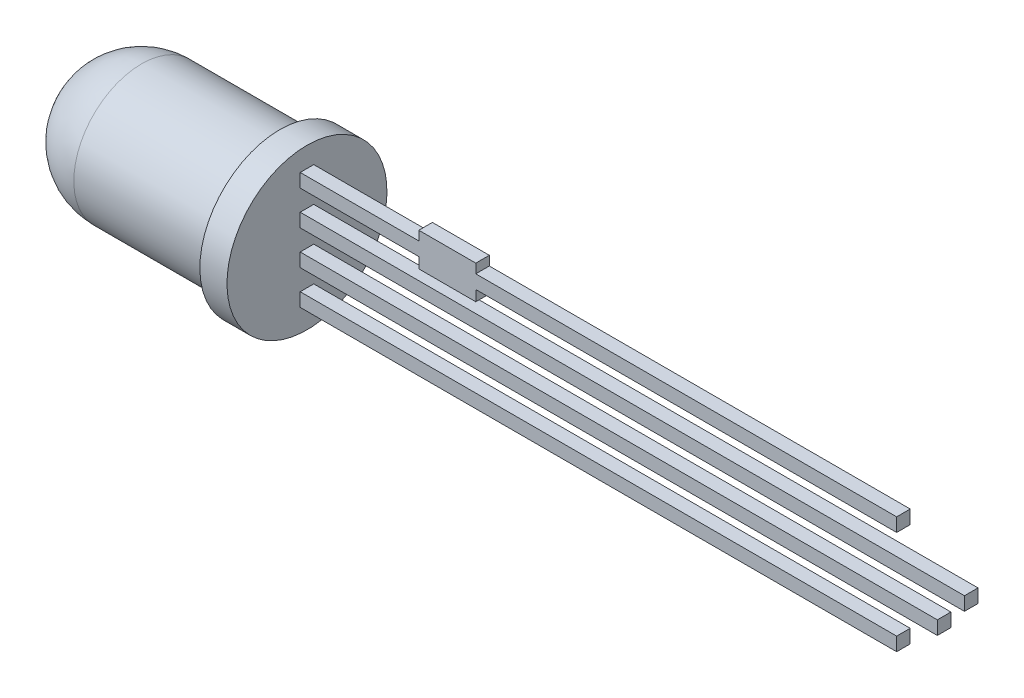
SolidWorks part; units mm, degrees
ref_plane "Front Plane" through (0, 0, 0) normal (0, 0, 1) x (1, 0, 0)
ref_plane "Top Plane" through (0, 0, 0) normal (0, 1, 0) x (1, 0, 0)
ref_plane "Right Plane" through (0, 0, 0) normal (1, 0, 0) x (0, 0, -1)
sketch "Sketch1" plane through (0, 0, 0) normal (0, 0, 1) x (1, 0, 0)
  line L0 (-6, 0) -> (-6, -2.95)
  line L1 (0, 0) -> (-6, 0) construction
  line L2 (-6, -2.95) -> (-7, -2.95)
  line L3 (-7, -2.95) -> (-7, -2.5)
  line L4 (-7, -2.5) -> (-12.1, -2.5)
  line L5 (-6, 0) -> (-14.6, 0) construction
  line L6 (-6, 0) -> (-14.6, 0)
  arc A0 (-14.6, 0) -> (-12.1, -2.5) centre (-12.1, 0) ccw
  point P9 (0, 0)
  point P10 (-14.6143, 0)
  dimension "D1" = 2.95
  dimension "D2" = 1
  dimension "D3" = 5
  dimension "D4" = 8.6
  dimension "D5" = 6
  dimension "D6" = 2.5
revolve "Revolve1" add sketch "Sketch1" angle 360 about L6
sketch "Sketch2" plane through (0, 0, 0) normal (0, 0, 1) x (1, 0, 0)
  line L0 (-6, 2.2047) -> (16, 2.2047)
  line L2 (-6, -2.95) -> (-6, 2.95) construction
  line L3 (16, 2.2047) -> (16, 1.7047)
  line L4 (16, 1.7047) -> (-6, 1.7047)
  line L5 (-6, 1.7047) -> (-6, 0.9347)
  line L6 (-6, 0.9347) -> (18.5, 0.9347)
  line L7 (18.5, 0.9347) -> (18.5, 0.4347)
  line L8 (18.5, 0.4347) -> (-6, 0.4347)
  line L9 (-6, 0.4347) -> (-6, -0.3353)
  line L10 (-6, -0.3353) -> (17.5, -0.3353)
  line L11 (17.5, -0.3353) -> (17.5, -0.8353)
  line L12 (17.5, -0.8353) -> (-6, -0.8353)
  line L13 (-6, -0.8353) -> (-6, -1.6053)
  line L14 (-6, -1.6053) -> (16, -1.6053)
  line L15 (16, -1.6053) -> (16, -2.1053)
  line L16 (16, -2.1053) -> (-6, -2.1053)
  line L17 (-6, -2.1053) -> (-6, 2.2047)
  line L19 (-1.6237, 2.5471) -> (0.4764, 2.5471)
  line L20 (-1.6237, 2.5471) -> (-1.6237, 1.3118)
  line L21 (-1.6237, 1.3118) -> (0.4764, 1.3118)
  line L22 (0.4764, 2.5471) -> (0.4764, 1.3118)
  dimension "D1" = 0.5
  dimension "D2" = 0.5
  dimension "D3" = 0.5
  dimension "D4" = 0.5
  dimension "D5" = 1.27
  dimension "D6" = 1.27
  dimension "D7" = 1.27
  dimension "D8" = 24.5
  dimension "D9" = 2.5
  dimension "D10" = 2.5
  dimension "D11" = 1
extrude "Boss-Extrude1" add sketch "Sketch2" along normal blind 0.25 and the other way blind 0.25 contours L17 L4 L3 L0 | L17 L8 L7 L6 | L17 L12 L11 L10 | L17 L16 L15 L14 | L20 L0 L17 L4 | L19 L22 L21 L20 region at (5, -1.8553, 0) region at (5.75, -0.5853, 0) region at (6.25, 0.6847, 0) region at (-3.8119, 1.9547, 0) region at (8.2382, 1.9547, 0)
